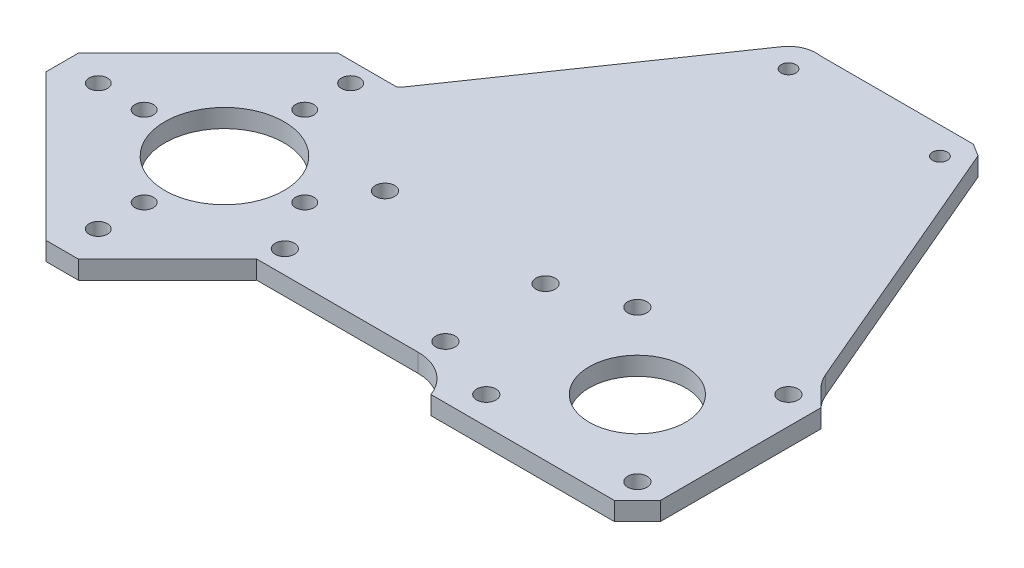
SolidWorks part; units mm, degrees
ref_plane "前视基准面" through (0, 0, 0) normal (0, 0, 1) x (1, 0, 0)
ref_plane "上视基准面" through (0, 0, 0) normal (0, 1, 0) x (1, 0, 0)
ref_plane "右视基准面" through (0, 0, 0) normal (1, 0, 0) x (0, 0, -1)
sketch "草图1" plane through (0, 0, 0) normal (0, 1, 0) x (1, 0, 0)
  line L0 (0, 0) -> (-31.8198, 0) construction
  line L1 (0, 31.8198) -> (-31.8198, 0)
  line L2 (-31.8198, 0) -> (0, -31.8198)
  line L3 (0, -31.8198) -> (15.9099, -15.9099)
  line L4 (15.9099, 15.9099) -> (0, 31.8198)
  line L5 (0, 0) -> (90, 0) construction
  line L6 (0, 0) -> (45, 77.9423) construction
  line L7 (45, 77.9423) -> (90, 0) construction
  line L8 (15.9099, 15.9099) -> (67.5, 15.9099)
  line L9 (15.9099, -15.9099) -> (67.5, -15.9099)
  line L10 (90, 0) -> (67.5, -22.5) construction
  line L11 (67.5, 22.5) -> (67.5, 15.9099)
  line L12 (67.5, -22.5) -> (112.5, -22.5)
  line L13 (112.5, -22.5) -> (112.5, 22.5)
  line L14 (112.5, 22.5) -> (67.5, 22.5)
  line L15 (67.5, -15.9099) -> (67.5, -22.5)
  line L16 (0, 0) -> (15.9099, 15.9099) construction
  line L17 (0, 0) -> (15.9099, -15.9099) construction
  circle A0 centre (0, 14) radius 2.1
  circle A1 centre (14, 0) radius 2.1
  circle A2 centre (0, -14) radius 2.1
  circle A3 centre (-14, 0) radius 2.1
  circle A4 centre (0, 0) radius 22.5 construction
  arc A5 (45, -77.9423) -> (45, 77.9423) centre (0, 0) ccw construction
  arc A6 (45, 77.9423) -> (45, -77.9423) centre (90, 0) ccw construction
  circle A7 centre (90, 0) radius 10.5
  circle A8 centre (90, 0) radius 22.5 construction
  circle A9 centre (0, 22.5) radius 2.1
  circle A11 centre (0, -22.5) radius 2.1
  circle A12 centre (0, 0) radius 10
  circle A13 centre (0, 0) radius 14 construction
  circle A14 centre (-22.5, 0) radius 2.1
  dimension "D1" = 4.2
  dimension "D2" = 20
  dimension "D3" = 4.2
  dimension "D4" = 4.2
  dimension "D5" = 4.2
  dimension "D6" = 45
  dimension "D9" = 180
  dimension "D10" = 180
  dimension "D11" = 21
  dimension "D14" = 4.2
  dimension "D15" = 4.2
  dimension "D17" = 4.2
  dimension "D7" = 180
  dimension "D8" = 90
  dimension "D12" = 135
  dimension "D13" = 45
extrude "凸台-拉伸1" add sketch "草图1" along normal blind 4
chamfer "倒角1" distance 5 angle 45 5 edges at (112.5, 2, 22.5) (112.5, 2, -22.5) (0, 2, 31.8198) (-31.8198, 2, 0) (0, 2, -31.8198)
fillet "圆角1" radius 10 4 edges at (15.9099, 2, -15.9099) (15.9099, 2, 15.9099) (67.5, 2, 15.9099) (67.5, 2, -15.9099)
sketch "草图2" plane through (0, 0, 0) normal (0, -1, 0) x (1, 0, 0)
  line L0 (39.0757, 15.9099) -> (39.0757, 10.9099) construction
  line L1 (20.052, 15.9099) -> (58.0993, 15.9099) construction
  line L2 (39.0757, 10.9099) -> (24.0757, 10.9099) construction
  line L3 (39.0757, 10.9099) -> (59.0757, 10.9099) construction
  line L4 (110, 20) -> (90, 0) construction
  line L5 (112.5, 17.5) -> (107.5, 22.5) construction
  line L6 (110, -20) -> (90, 0) construction
  line L7 (107.5, -22.5) -> (112.5, -17.5) construction
  line L8 (90, 22.5) -> (90, -22.5) construction
  line L9 (67.5, 22.5) -> (107.5, 22.5) construction
  line L10 (107.5, -22.5) -> (67.5, -22.5) construction
  line L11 (70, -20) -> (90, 0) construction
  line L12 (70, 20) -> (90, 0) construction
  line L13 (0, 0) -> (90, 0) construction
  line L14 (39.0757, -10.9099) -> (59.0757, -10.9099) construction
  line L15 (39.0757, -10.9099) -> (24.0757, -10.9099) construction
  line L16 (39.0757, -15.9099) -> (39.0757, -10.9099) construction
  circle A0 centre (106.4645, 16.4645) radius 2.1
  circle A1 centre (106.4645, -16.4645) radius 2.1
  circle A2 centre (73.5355, -16.4645) radius 2.1
  circle A3 centre (73.5355, 16.4645) radius 2.1
  circle A4 centre (24.0757, 10.9099) radius 2.1
  circle A5 centre (59.0757, 10.9099) radius 2.1
  circle A6 centre (59.0757, -10.9099) radius 2.1
  circle A7 centre (24.0757, -10.9099) radius 2.1
  dimension "D3" = 4.2
  dimension "D4" = 4.2
  dimension "D5" = 20
  dimension "D6" = 15
  dimension "D8" = 4.2
  dimension "D9" = 4.2
  dimension "D1" = 5
  dimension "D2" = 5
  dimension "D7" = 5
extrude "切除-拉伸1" cut sketch "草图2" against normal blind 10
sketch "草图3" plane through (0, 4, 0) normal (0, 1, 0) x (1, 0, 0)
  line L0 (0, 0) -> (90, 0) construction
  line L1 (45, 0) -> (45, 77.9423) construction
  line L2 (3.5355, 28.2843) -> (40.0576, 81.3442)
  line L3 (67.5, 22.5) -> (50.7578, 79.6297)
  line L4 (12.981, 18.8388) -> (3.5355, 28.2843) construction
  line L5 (58.0993, 15.9099) -> (20.052, 15.9099) construction
  line L6 (12.981, 18.8388) -> (3.5355, 28.2843)
  line L7 (58.0993, 15.9099) -> (20.052, 15.9099)
  line L8 (16.4918, 29.4702) -> (43.5266, 68.7468)
  line L9 (56.0801, 25.9099) -> (43.5266, 68.7468)
  line L10 (56.0801, 25.9099) -> (20.052, 25.9099)
  line L11 (20.052, 25.9099) -> (16.4918, 29.4702)
  circle A0 centre (45, 77.9423) radius 1.6
  arc A1 (50.7578, 79.6297) -> (40.0576, 81.3442) centre (45, 77.9423) ccw
  arc A2 (12.981, 18.8388) -> (20.052, 15.9099) centre (20.052, 25.9099) ccw construction
  arc A3 (58.0993, 15.9099) -> (67.5, 22.5) centre (58.0993, 25.9099) ccw construction
  arc A4 (12.981, 18.8388) -> (20.052, 15.9099) centre (20.052, 25.9099) ccw
  arc A5 (58.0993, 15.9099) -> (67.5, 22.5) centre (58.0993, 25.9099) ccw
  arc A6 (43.5266, 68.7468) -> (43.5266, 68.7468) centre (43.5266, 68.7468) ccw
  arc A7 (56.0801, 25.9099) -> (56.0801, 25.9099) centre (56.0801, 25.9099) ccw
  arc A8 (20.052, 25.9099) -> (20.052, 25.9099) centre (20.052, 25.9099) ccw
  dimension "D1" = 3.2
  dimension "D2" = 12
  dimension "D3" = 10
extrude "凸台-拉伸2" add sketch "草图3" against normal blind 4
fillet "圆角2" radius 3 4 edges at (20.052, 2, -25.9099) (16.4918, 2, -29.4702) (56.0801, 2, -25.9099) (43.5266, 2, -68.7468)
fillet "圆角3" radius 11 2 edges at (3.5355, 2, -28.2843) (67.5, 2, -22.5)
sketch "草图4" plane through (0, 4, 0) normal (0, 1, 0) x (1, 0, 0)
  line L0 (45.9493, 83.8667) -> (81.3477, 83.8667)
  line L3 (81.3477, 83.8667) -> (107.5, 22.5)
  line L4 (52.1537, 74.8667) -> (75.4, 74.8667)
  line L5 (75.4, 74.8667) -> (97.7168, 22.5)
  line L6 (107.5, 22.5) -> (75.739, 22.5) construction
  line L7 (73.0682, 80.3383) -> (99.2205, 18.9716) construction
  line L8 (45.9493, 74.8667) -> (90, 74.8667) construction
  line L9 (107.5, 22.5) -> (97.7168, 22.5)
  line L10 (65.183, 30.4065) -> (50.7578, 79.6297) construction
  line L11 (52.1537, 74.8667) -> (50.7578, 79.6297)
  line L12 (45.9493, 83.8667) -> (90, 83.8667) construction
  arc A0 (50.7578, 79.6297) -> (40.0576, 81.3442) centre (45, 77.9423) ccw construction
  circle A2 centre (78, 77.9423) radius 1.6
  arc A3 (50.7578, 79.6297) -> (45.9493, 83.8667) centre (45, 77.9423) ccw
  dimension "D1" = 33
extrude "凸台-拉伸3" add sketch "草图4" against normal blind 4
fillet "圆角4" radius 10 3 edges at (75.4, 2, -74.8667) (97.7168, 2, -22.5) (52.1537, 2, -74.8667)
chamfer "倒角2" distance 2 angle 32 1 edges at (81.3477, 2, -83.8667) first distance on face at (63.6485, 2, -83.8667)
fillet "圆角5" radius 10 1 edges at (107.5, 2, -22.5)
sketch "草图5" plane through (0, 4, 0) normal (0, 1, 0) x (1, 0, 0)
  line L0 (-3.5355, 28.2843) -> (-39.0616, -7.2418)
  line L1 (-3.5355, -28.2843) -> (-42.3493, 10.5295)
  line L2 (12.981, -18.8388) -> (-5.1917, -37.0115)
  line L3 (-3.5355, -28.2843) -> (8.3919, -40.2117)
  line L4 (-6.4348, 32.4561) -> (-46.5266, -7.6357)
  line L5 (-3.5355, 28.2843) -> (-14.4637, 39.2124)
  line L6 (-44.8598, 5.9689) -> (2.5215, -41.4124)
  line L7 (-3.0285, -41.9194) -> (18.4931, -20.3978)
  line L9 (18.4931, -20.3978) -> (31.6491, -7.2418)
  line L10 (22.9362, -15.9547) -> (16.5268, -9.5453)
  line L11 (16.5268, -9.5453) -> (29.289, 3.2169)
  line L12 (-7.0711, 31.8198) -> (8.8805, 31.8198)
  line L13 (5.8328, 31.8198) -> (26.5977, 0.5256)
  line L14 (-35.3553, 3.5355) -> (-35.3553, -3.5355)
  line L15 (-3.5355, -35.3553) -> (3.5355, -35.3553)
  arc A0 (-2.2469, 28.2843) -> (6.8141, 33.0474) centre (-2.2469, 39.2843) ccw construction
  circle A1 centre (0, 0) radius 11.2371
  dimension "D1" = 5
  dimension "D2" = 5
  dimension "D3" = 5
extrude "凸台-拉伸4" add sketch "草图5" against normal blind 4 contours L0 L5 L4 L1 | L13 L12 L5 L0 L1 L3 L7 L9 L10 L11 A1 | L1 L14 L0 | L0 L6 L2 L3 L1 | L2 L15 L3 region at (-4.6738, 4, -30.6815) region at (-19.4454, 4, -15.9099) region at (-17.6777, 4, 17.6777) region at (-34.1768, 4, 0) region at (0, 4, 34.1768)
sketch "草图6" plane through (0, 4, 0) normal (0, 1, 0) x (1, 0, 0)
  line L0 (0, 30.6524) -> (0, -43.684)
  line L1 (-33.9572, 0) -> (63.6804, 0)
  circle A0 centre (0, 27.5) radius 2
  circle A1 centre (-27.5, 0) radius 2
  circle A2 centre (0, -27.5) radius 2
  dimension "D1" = 4
  dimension "D2" = 4
  dimension "D3" = 4
  dimension "D4" = 27.5
  dimension "D5" = 27.5
  dimension "D6" = 27.5
extrude "凸台-拉伸5" add sketch "草图6" against normal blind 14 separate body contours L0 A0 | L0 A0 | L1 A1 | L0 A2 | L0 A2 | A1 region at (0.8488, 4, -27.5) region at (0.8488, 4, 27.5) region at (-0.8488, 4, 27.5) region at (-27.5, 4, -0.8488) region at (-0.8488, 4, -27.5)
combine bodies "组合1" operation type subtract main body 110 bodies to subtract 111 112 113
sketch "草图7" plane through (0, 4, 0) normal (0, 1, 0) x (1, 0, 0)
  circle A0 centre (0, 0) radius 13
  dimension "D1" = 26
extrude "凸台-拉伸6" add sketch "草图7" against normal blind 14 separate body
combine bodies "组合2" operation type subtract main body 114 bodies to subtract 115
sketch "草图8" plane through (0, 4, 0) normal (0, 1, 0) x (1, 0, 0)
  circle A0 centre (0, 0) radius 17.5
  dimension "D1" = 35
sketch "草图9" plane through (0, 4, 0) normal (0, 1, 0) x (1, 0, 0)
  line L0 (0, 21.2955) -> (0, -22.3737)
  line L1 (-21.6676, 0) -> (35.4262, 0)
  circle A0 centre (0, 17.5) radius 2
  circle A1 centre (0, 0) radius 17.5 construction
  circle A2 centre (17.5, 0) radius 2
  circle A3 centre (-17.5, 0) radius 2
  circle A4 centre (0, -17.5) radius 2
  dimension "D1" = 4
  dimension "D2" = 4
  dimension "D3" = 4
  dimension "D4" = 4
extrude "凸台-拉伸7" add sketch "草图9" against normal blind 14 separate body contours L0 A0 | L0 A0 | L1 A3 | L1 A3 | L1 A2 | L1 A2 | L0 A4 | L0 A4 region at (0.8488, 4, -17.5) region at (17.5, 4, -0.8488) region at (17.5, 4, 0.8488) region at (0.8488, 4, 17.5) region at (-0.8488, 4, 17.5) region at (-17.5, 4, 0.8488) region at (-17.5, 4, -0.8488) region at (-0.8488, 4, -17.5)
combine bodies "组合3" operation type subtract main body 116 bodies to subtract 117 120 118 119
sketch "草图10" plane through (0, 4, 0) normal (0, 1, 0) x (1, 0, 0)
  line L0 (38.788, 70.6173) -> (7.3534, 23.5629)
  line L1 (7.3534, 23.5629) -> (103.7067, 21.101)
  line L2 (103.7067, 21.101) -> (80.4866, 74.9257)
  line L3 (80.4866, 74.9257) -> (61.534, 75.41)
  line L4 (61.534, 75.41) -> (38.788, 70.6173)
extrude "凸台-拉伸8" add sketch "草图10" against normal blind 4
